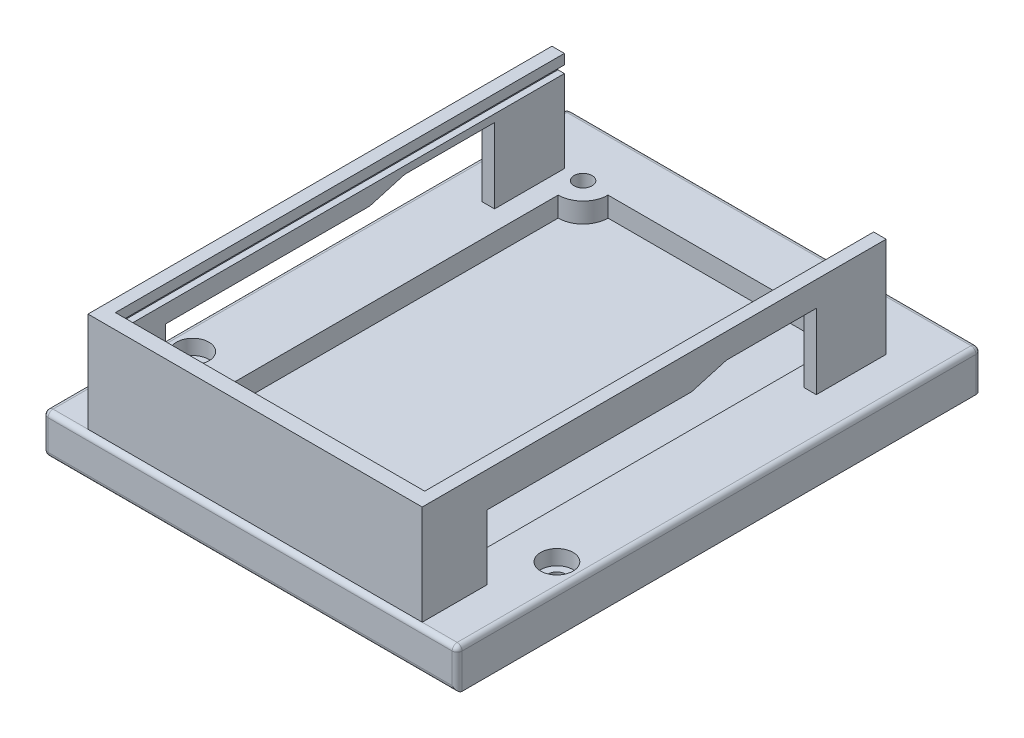
SolidWorks part; units mm, degrees
ref_plane "Front Plane" through (0, 0, 0) normal (0, 0, 1) x (1, 0, 0)
ref_plane "Top Plane" through (0, 0, 0) normal (0, 1, 0) x (1, 0, 0)
ref_plane "Right Plane" through (0, 0, 0) normal (1, 0, 0) x (0, 0, -1)
sketch "Sketch1" plane through (0, 0, 0) normal (0, 1, 0) x (1, 0, 0)
  line L0 (41.5, 95) -> (41.5, 0) construction
  line L1 (0, 0) -> (83, 0)
  line L2 (0, 0) -> (0, 105)
  line L3 (0, 105) -> (83, 105)
  line L4 (83, 0) -> (83, 105)
  line L5 (14.475, 93.775) -> (14.475, 11.225) construction
  circle A0 centre (5, 25) radius 1.75
  circle A1 centre (14.475, 11.225) radius 1.65 construction
  circle A2 centre (14.475, 93.775) radius 1.65 construction
  circle A3 centre (78, 25) radius 1.75
  circle A4 centre (68.525, 11.225) radius 1.65 construction
  circle A5 centre (68.525, 93.775) radius 1.65 construction
  point P19 (14.475, 52.5)
  point P20 (41.5, 0)
  point P21 (0, 52.5)
  dimension "D2" = 36.5
  dimension "D3" = 3.5
  dimension "D5" = 13.775
  dimension "D6" = 27.025
  dimension "D7" = 3.3
  dimension "D9" = 82.55
  dimension "D10" = 3.3
  dimension "D1" = 83
  dimension "D4" = 105
extrude "Boss-Extrude1" add sketch "Sketch1" along normal blind 8
sketch "Sketch3" plane through (0, 0, 0) normal (0, -1, 0) x (1, 0, 0)
  point P0 (14.475, -11.225)
  point P1 (68.525, -11.225)
  point P3 (68.525, -93.775)
  point P5 (14.475, -93.775)
hole_wizard "CBORE for M3 SHCS1" positions "Sketch3" profile "Sketch4" counterbore size "M3" standard "ANSI Metric" end condition through all
sketch "Sketch4" plane through (14.475, 0, -11.225) normal (1, 0, 0) x (0, 0, -1)
  line L0 (0, 0) -> (0, 8)
  line L1 (0, 8) -> (1.8, 8)
  line L3 (1.8, 8) -> (1.8, 3)
  line L4 (1.8, 3) -> (3.25, 3)
  line L5 (3.25, 3) -> (3.25, 0)
  line L7 (3.25, 0) -> (0, 0)
  line L11 (0, -6.35) -> (0, 107.95) construction
  dimension "Thru Hole Dia." = 3.6
  dimension "Thru Hole Depth" = 8
  dimension "C'Bore Dia." = 6.5
  dimension "C'Bore Depth" = 3
sketch "Sketch5" plane through (0, 8, 0) normal (0, 1, 0) x (1, 0, 0)
  line L1 (19.475, 93.775) -> (63.525, 93.775)
  line L2 (14.475, 88.775) -> (14.475, 16.225)
  line L3 (19.475, 11.225) -> (63.525, 11.225)
  line L4 (68.525, 88.775) -> (68.525, 16.225)
  line L5 (41.5, 200095) -> (41.5, -200000) construction
  circle A0 centre (14.475, 93.775) radius 1.65 construction
  circle A1 centre (14.475, 11.225) radius 1.65 construction
  arc A3 (14.475, 88.775) -> (19.475, 93.775) centre (14.475, 93.775) ccw
  arc A4 (63.525, 93.775) -> (68.525, 88.775) centre (68.525, 93.775) ccw
  arc A5 (68.525, 16.225) -> (63.525, 11.225) centre (68.525, 11.225) ccw
  arc A6 (19.475, 11.225) -> (14.475, 16.225) centre (14.475, 11.225) ccw
  dimension "D3" = 54.05
  dimension "D4" = 27.025
  dimension "D1" = 0
  dimension "D2" = 0
extrude "Cut-Extrude1" cut sketch "Sketch5" against normal blind 4
sketch "Sketch6" plane through (0, 0, 0) normal (0, -1, 0) x (1, 0, 0)
  line L1 (11.475, -35) -> (16.475, -35)
  line L2 (11.475, -35) -> (11.475, -55)
  line L3 (11.475, -55) -> (16.475, -55)
  line L4 (16.475, -35) -> (16.475, -55)
  dimension "D1" = 5
  dimension "D2" = 20
  dimension "D3" = 3
  dimension "D4" = 10
extrude "Boss-Extrude2" add sketch "Sketch6" along normal blind 8.8
sketch "Sketch7" plane through (0, 0, -55) normal (0, 0, -1) x (-1, 0, 0)
  line L0 (-16.475, -8.8) -> (-16.475, 0) construction
  line L1 (-11.475, 0) -> (-14.675, 0)
  line L2 (-11.475, 0) -> (-11.475, -6.8)
  line L3 (-11.475, -6.8) -> (-14.675, -6.8)
  line L4 (-14.675, 0) -> (-14.675, -6.8)
  dimension "D1" = 6.8
  dimension "D2" = 1.8
extrude "Cut-Extrude2" cut sketch "Sketch7" against normal through all
fillet "Fillet1" radius 6 1 edges at (16.475, 0, -45) second distance 8 first distance on face at (14.475, 0, -14.475)
fillet "Fillet2" radius 1 10 edges at (0, 4, 0) (41.5, 8, 0) (83, 4, 0) (83, 4, -105) (83, 8, -52.5) (41.5, 8, -105) (0, 4, -105) (0, 8, -52.5) (0, 0, -52.5) (41.5, 0, 0)
sketch "Sketch8" plane through (0, 8, 0) normal (0, 1, 0) x (1, 0, 0)
  line L1 (8, 94) -> (75, 94)
  line L2 (8, 94) -> (8, 1)
  line L3 (8, 1) -> (75, 1)
  line L4 (75, 94) -> (75, 1)
  line L6 (1, 1) -> (82, 1) construction
  circle A4 centre (5, 25) radius 1.75 construction
  dimension "D1" = 3
  dimension "D3" = 93
  dimension "D2" = 3
  dimension "D4" = 0
extrude "Boss-Extrude4" add sketch "Sketch8" along normal blind 20
sketch "Sketch11" plane through (0, 0, -94) normal (0, 0, -1) x (-1, 0, 0)
  line L0 (-75, 8) -> (-70.3109, 8) construction
  line L1 (-72.5, 8) -> (-10.5, 8)
  line L2 (-72.5, 8) -> (-72.5, 24.5)
  line L3 (-72.5, 28) -> (-10.5, 28)
  line L4 (-10.5, 8) -> (-10.5, 24.5)
  line L5 (-75, 28) -> (-75, 8) construction
  line L6 (-8, 28) -> (-8, 8) construction
  line L7 (-75, 28) -> (-8, 28) construction
  line L8 (-10.5, 24.5) -> (-9.2, 24.5)
  line L9 (-73.8, 26) -> (-72.5, 26)
  line L10 (-73.8, 26) -> (-73.8, 24.5)
  line L11 (-73.8, 24.5) -> (-72.5, 24.5)
  line L12 (-9.2, 26) -> (-9.2, 24.5)
  line L13 (-10.5, 26) -> (-9.2, 26)
  line L14 (-72.5, 26) -> (-72.5, 28)
  line L15 (-10.5, 26) -> (-10.5, 28)
  dimension "D1" = 2.5
  dimension "D2" = 2.5
  dimension "D3" = 0
  dimension "D4" = 1.2
  dimension "D5" = 1.5
  dimension "D6" = 1.2
  dimension "D7" = 2
extrude "Cut-Extrude3" cut sketch "Sketch11" against normal blind 90
sketch "Sketch12" plane through (0, 0, -4) normal (0, 0, -1) x (-1, 0, 0)
  line L1 (-73.8, 26) -> (-9.2, 26)
  line L2 (-73.8, 26) -> (-73.8, 24.5)
  line L3 (-73.8, 24.5) -> (-9.2, 24.5)
  line L4 (-9.2, 26) -> (-9.2, 24.5)
extrude "Cut-Extrude4" cut sketch "Sketch12" against normal blind 1
sketch "Sketch15" plane through (75, 0, 0) normal (1, 0, 0) x (0, 0, -1)
  line L0 (1, 8) -> (104, 8) construction
  line L1 (55, 8) -> (37, 8)
  line L2 (55, 8) -> (55, 21) construction
  line L3 (55, 21) -> (37, 21)
  line L4 (37, 8) -> (37, 21) construction
  line L5 (32, 21) -> (37, 21)
  line L6 (1, 8) -> (94, 8) construction
  line L7 (32, 8) -> (14, 8)
  line L8 (32, 8) -> (32, 21) construction
  line L9 (32, 21) -> (14, 21)
  line L10 (14, 8) -> (14, 21)
  line L11 (1, 28) -> (1, 8) construction
  line L12 (32, 8) -> (37, 8)
  line L13 (55, 21) -> (62, 23)
  line L14 (62, 23) -> (80, 23)
  line L15 (62, 23) -> (62, 8) construction
  line L16 (62, 8) -> (80, 8)
  line L17 (80, 23) -> (80, 8)
  line L18 (55, 8) -> (62, 8)
  dimension "D1" = 18
  dimension "D2" = 13
  dimension "D3" = 13
  dimension "D4" = 18
  dimension "D5" = 13
  dimension "D6" = 5
  dimension "D7" = 18
  dimension "D8" = 15
  dimension "D9" = 7
extrude "Cut-Extrude5" cut sketch "Sketch15" against normal through all and the other way through all
sketch "Sketch16" plane through (0, 8, 0) normal (0, 1, 0) x (1, 0, 0)
  point P0 (5, 25)
  point P1 (78, 25)
hole_wizard "CBORE for M3 SHCS2" positions "Sketch16" profile "Sketch17" counterbore size "M3" standard "ANSI Metric" end condition through all
sketch "Sketch17" plane through (5, 8, -25) normal (1, 0, 0) x (0, 0, 1)
  line L0 (0, 0) -> (0, 16.8)
  line L1 (0, 16.8) -> (1.7, 16.8)
  line L3 (1.7, 16.8) -> (1.7, 3)
  line L4 (1.7, 3) -> (3.25, 3)
  line L5 (3.25, 3) -> (3.25, 0)
  line L7 (3.25, 0) -> (0, 0)
  line L11 (0, -6.35) -> (0, 107.95) construction
  dimension "Thru Hole Dia." = 3.4
  dimension "Thru Hole Depth" = 16.8
  dimension "C'Bore Dia." = 6.5
  dimension "C'Bore Depth" = 3
